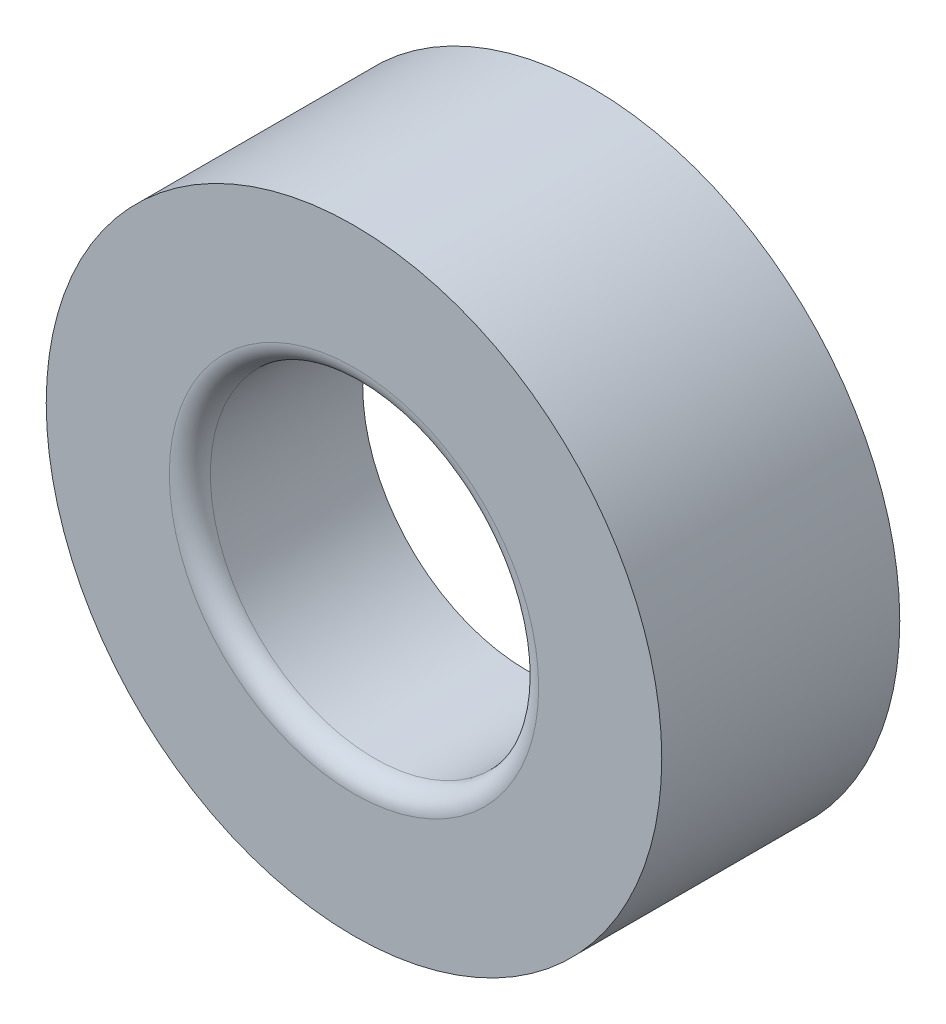
SolidWorks part; units mm, degrees
ref_plane "Front Plane" through (0, 0, 0) normal (0, 0, 1) x (1, 0, 0)
ref_plane "Top Plane" through (0, 0, 0) normal (0, 1, 0) x (1, 0, 0)
ref_plane "Right Plane" through (0, 0, 0) normal (1, 0, 0) x (0, 0, -1)
sketch "Sketch1" plane through (0, 0, 0) normal (0, 0, 1) x (1, 0, 0)
  circle A0 centre (85.2065, -1.764) radius 7.5
  dimension "D1" = 15
extrude "Boss-Extrude1" add sketch "Sketch1" along normal blind 5.8
sketch "Sketch2" plane through (0, 0, 5.8) normal (0, 0, 1) x (1, 0, 0)
  circle A0 centre (85.2065, -1.764) radius 4
  dimension "D1" = 8
extrude "Cut-Extrude1" cut sketch "Sketch2" against normal through all
sketch "Sketch3" plane through (0, 0, 0) normal (0, 0, -1) x (-1, 0, 0)
  circle A0 centre (-85.2065, -1.764) radius 6.4
  dimension "D1" = 12.8
extrude "Cut-Extrude2" cut sketch "Sketch3" against normal blind 1.5875
fillet "Fillet1" radius 0.5 1 edges at (89.2065, -1.764, 5.8)
